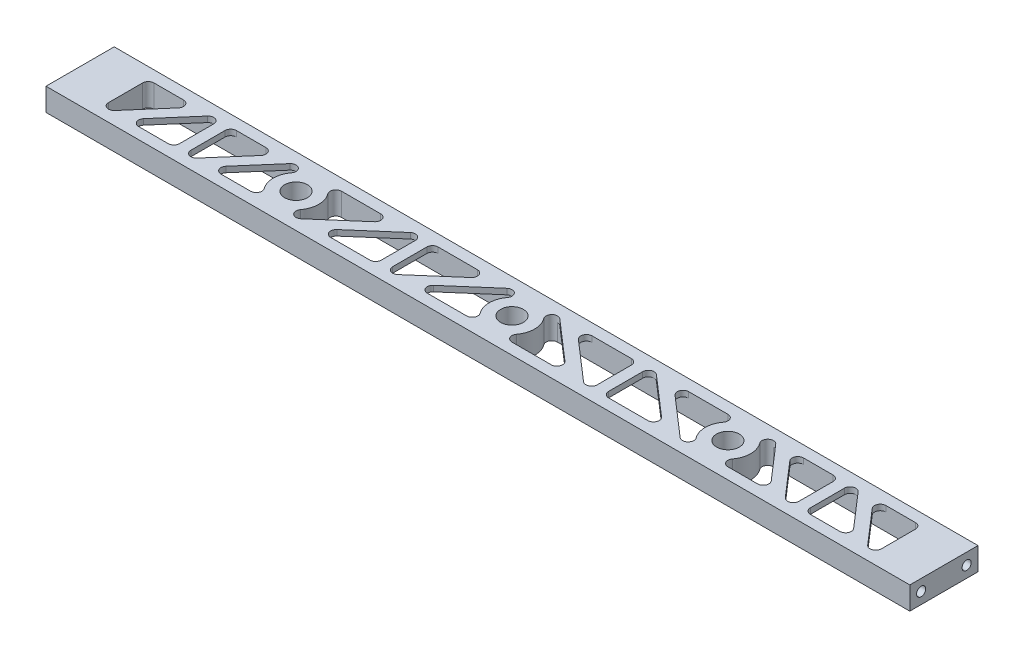
SolidWorks part; units mm, degrees
material "6061 Alloy"
ref_plane "Front Plane" through (0, 0, 0) normal (0, 0, 1) x (1, 0, 0)
ref_plane "Top Plane" through (0, 0, 0) normal (0, 1, 0) x (1, 0, 0)
ref_plane "Right Plane" through (0, 0, 0) normal (1, 0, 0) x (0, 0, -1)
sketch "Sketch1" plane through (0, 0, 0) normal (1, 0, 0) x (0, 0, -1)
  line L1 (-19.05, -6.35) -> (19.05, -6.35)
  line L2 (-19.05, -6.35) -> (-19.05, 6.35)
  line L3 (-19.05, 6.35) -> (19.05, 6.35)
  line L4 (19.05, -6.35) -> (19.05, 6.35)
  line L5 (-19.05, -6.35) -> (19.05, 6.35) construction
  line L6 (-19.05, 6.35) -> (19.05, -6.35) construction
  point P0 (0, 0)
  dimension "D1" = 38.1
  dimension "D2" = 12.7
extrude "Boss-Extrude1" add sketch "Sketch1" along normal mid plane 482.6
hole_wizard "1/4-20 Tapped Hole1" positions "3DSketch1" profile "Sketch3" tap size "1/4-20" standard "ANSI Inch"
sketch3d "3DSketch1"
  line L4 (241.3, 0, 19.05) -> (241.3, 0, 12.7) construction
  line L5 (241.3, 6.35, 19.05) -> (241.3, -6.35, 19.05) construction
  line L6 (241.3, 0, 12.7) -> (241.3, 0, -12.7) construction
  line L7 (241.3, 0, -12.7) -> (241.3, 0, -19.05) construction
  line L8 (241.3, -6.35, -19.05) -> (241.3, 6.35, -19.05) construction
  point P0 (241.3, 0, 12.7)
  point P2 (241.3, 0, -12.7)
  dimension "D1" = 25.4
sketch "Sketch3" plane through (241.3, 0, 12.7) normal (0, 1, 0) x (0, 0, -1)
  line L0 (0, 0) -> (0, 20.5838)
  line L1 (0, 20.5838) -> (2.5527, 19.05)
  line L2 (2.5527, 19.05) -> (2.5527, 0)
  line L5 (2.5527, 0) -> (0, 0)
  line L10 (0, 20.5838) -> (-2.5527, 19.05) construction
  line L11 (0, -6.35) -> (0, 107.95) construction
  dimension "Tap Drill Dia." = 5.1054
  dimension "Tap Drill Depth" = 19.05
  dimension "Drill Angle" = 118
sketch "Sketch2" plane through (0, 6.35, 0) normal (0, 1, 0) x (1, 0, 0)
  line L0 (0, 0) -> (241.3, 0) construction
  line L1 (241.3, -19.05) -> (241.3, 19.05) construction
  circle A0 centre (0, 0) radius 6.35
  circle A1 centre (120.65, 0) radius 6.35
  dimension "D1" = 12.7
extrude "Cut-Extrude1" cut sketch "Sketch2" against normal through all
sketch "Sketch4" plane through (0, -6.35, 0) normal (0, -1, 0) x (1, 0, 0)
  line L1 (12.7, 12.7) -> (107.95, 12.7)
  line L2 (133.35, 12.7) -> (212.725, 12.7)
  line L3 (215.9, 9.525) -> (215.9, -9.525)
  line L4 (212.725, -12.7) -> (133.35, -12.7)
  line L5 (107.95, -12.7) -> (12.7, -12.7)
  line L6 (241.3, 0) -> (215.9, 0) construction
  line L8 (241.3, 19.05) -> (241.3, -19.05) construction
  line L9 (241.3, 19.05) -> (-241.3, 19.05) construction
  arc A0 (10.16, -7.62) -> (10.16, 7.62) centre (0, 0) ccw
  arc A1 (110.49, 7.62) -> (110.49, -7.62) centre (120.65, 0) ccw
  arc A2 (130.81, 7.62) -> (130.81, -7.62) centre (120.65, 0) cw
  arc A3 (130.81, 7.62) -> (133.35, 12.7) centre (133.35, 9.525) cw
  arc A4 (130.81, -7.62) -> (133.35, -12.7) centre (133.35, -9.525) ccw
  arc A5 (110.49, -7.62) -> (107.95, -12.7) centre (107.95, -9.525) cw
  arc A6 (215.9, -9.525) -> (212.725, -12.7) centre (212.725, -9.525) cw
  arc A7 (212.725, 12.7) -> (215.9, 9.525) centre (212.725, 9.525) cw
  arc A8 (10.16, -7.62) -> (12.7, -12.7) centre (12.7, -9.525) ccw
  arc A9 (10.16, 7.62) -> (12.7, 12.7) centre (12.7, 9.525) cw
  arc A10 (110.49, 7.62) -> (107.95, 12.7) centre (107.95, 9.525) ccw
  dimension "D3" = 25.4
  dimension "D4" = 3.175
  dimension "D1" = 12.7
  dimension "D2" = 6.35
extrude "Cut-Extrude2" cut sketch "Sketch4" against normal blind 9.525
mirror "Mirror2" about plane through (0, 0, 0) normal (1, 0, 0) of "Cut-Extrude2", "Cut-Extrude1", "1/4-20 Tapped Hole1"
sketch "Sketch5" plane through (0, 3.175, 0) normal (0, -1, 0) x (1, 0, 0)
  line L0 (0, 19.05) -> (0, -19.05) construction
  line L1 (241.3, 19.05) -> (-241.3, 19.05) construction
  line L2 (241.3, -19.05) -> (-241.3, -19.05) construction
  line L3 (-107.95, -12.7) -> (-86.0338, -12.7)
  line L4 (-105.8671, 11.9213) -> (-83.9509, -7.1287)
  line L5 (-88.5912, 12.7) -> (-66.675, 12.7)
  line L6 (-63.5, 9.525) -> (-63.5, -9.525)
  line L7 (-90.6741, 7.1287) -> (-68.7579, -11.9213)
  line L8 (-83.9509, -7.1287) -> (-79.7851, -2.3362) construction
  line L9 (-107.95, 12.7) -> (-12.7, 12.7) construction
  line L10 (-12.7, -12.7) -> (-107.95, -12.7) construction
  line L11 (-12.7, 12.7) -> (-34.6162, 12.7)
  line L12 (-14.7829, -11.9213) -> (-36.6991, 7.1287)
  line L13 (-57.15, 9.525) -> (-57.15, -9.525)
  line L14 (-53.975, -12.7) -> (-32.0588, -12.7)
  line L15 (-51.8921, 11.9213) -> (-29.9759, -7.1287)
  line L16 (-29.9759, -7.1287) -> (-25.8101, -2.3362) construction
  line L17 (-63.5, 0) -> (-57.15, 0) construction
  line L18 (-133.35, 12.7) -> (-149.8751, 12.7)
  line L19 (-152.2734, 7.4445) -> (-135.7484, -11.6055)
  line L20 (-212.725, 12.7) -> (-133.35, 12.7) construction
  line L21 (-164.2891, 11.6055) -> (-147.7641, -7.4445)
  line L22 (-150.1624, -12.7) -> (-166.6875, -12.7)
  line L23 (-169.8625, 9.525) -> (-169.8625, -9.525)
  line L24 (-133.35, -12.7) -> (-212.725, -12.7) construction
  line L25 (-152.2734, 7.4445) -> (-157.0702, 3.2835) construction
  line L26 (-176.2125, 9.525) -> (-176.2125, -9.525)
  line L27 (-179.3875, 12.7) -> (-195.9126, 12.7)
  line L28 (-198.3109, 7.4445) -> (-181.7859, -11.6055)
  line L29 (-210.3266, 11.6055) -> (-193.8016, -7.4445)
  line L30 (-196.1999, -12.7) -> (-212.725, -12.7)
  line L31 (-215.9, -9.525) -> (-215.9, 9.525) construction
  line L32 (-215.9, -9.525) -> (-215.9, 9.525)
  line L33 (-169.8625, 0) -> (-176.2125, 0) construction
  line L34 (-198.3109, 7.4445) -> (-203.1077, 3.2835) construction
  arc A0 (-110.49, 7.62) -> (-110.49, -7.62) centre (-120.65, 0) cw
  arc A1 (-105.8671, 11.9213) -> (-110.49, 7.62) centre (-107.95, 9.525) ccw
  arc A2 (-107.95, -12.7) -> (-110.49, -7.62) centre (-107.95, -9.525) cw
  arc A3 (-86.0338, -12.7) -> (-83.9509, -7.1287) centre (-86.0338, -9.525) ccw
  arc A5 (-68.7579, -11.9213) -> (-63.5, -9.525) centre (-66.675, -9.525) ccw
  arc A6 (-66.675, 12.7) -> (-63.5, 9.525) centre (-66.675, 9.525) cw
  arc A7 (-88.5912, 12.7) -> (-90.6741, 7.1287) centre (-88.5912, 9.525) ccw
  arc A8 (-110.49, -7.62) -> (-110.49, 7.62) centre (-120.65, 0) ccw construction
  arc A9 (-10.16, 7.62) -> (-12.7, 12.7) centre (-12.7, 9.525) ccw construction
  arc A10 (-10.16, 7.62) -> (-10.16, -7.62) centre (0, 0) ccw construction
  arc A12 (-10.16, 7.62) -> (-12.7, 12.7) centre (-12.7, 9.525) ccw
  arc A13 (-10.16, 7.62) -> (-10.16, -7.62) centre (0, 0) ccw
  arc A14 (-14.7829, -11.9213) -> (-10.16, -7.62) centre (-12.7, -9.525) ccw
  arc A15 (-12.7, -12.7) -> (-10.16, -7.62) centre (-12.7, -9.525) ccw construction
  arc A16 (-34.6162, 12.7) -> (-36.6991, 7.1287) centre (-34.6162, 9.525) ccw
  arc A17 (-57.15, 9.525) -> (-51.8921, 11.9213) centre (-53.975, 9.525) cw
  arc A18 (-57.15, -9.525) -> (-53.975, -12.7) centre (-53.975, -9.525) ccw
  arc A19 (-32.0588, -12.7) -> (-29.9759, -7.1287) centre (-32.0588, -9.525) ccw
  arc A20 (-130.81, 7.62) -> (-130.81, -7.62) centre (-120.65, 0) ccw
  arc A21 (-130.81, 7.62) -> (-130.81, -7.62) centre (-120.65, 0) ccw construction
  arc A22 (-149.8751, 12.7) -> (-152.2734, 7.4445) centre (-149.8751, 9.525) ccw
  arc A23 (-130.81, -7.62) -> (-135.7484, -11.6055) centre (-133.35, -9.525) cw
  arc A24 (-133.35, -12.7) -> (-130.81, -7.62) centre (-133.35, -9.525) ccw construction
  arc A25 (-130.81, 7.62) -> (-133.35, 12.7) centre (-133.35, 9.525) ccw
  arc A26 (-130.81, 7.62) -> (-133.35, 12.7) centre (-133.35, 9.525) ccw construction
  arc A27 (-164.2891, 11.6055) -> (-169.8625, 9.525) centre (-166.6875, 9.525) ccw
  arc A28 (-150.1624, -12.7) -> (-147.7641, -7.4445) centre (-150.1624, -9.525) ccw
  arc A29 (-166.6875, -12.7) -> (-169.8625, -9.525) centre (-166.6875, -9.525) cw
  arc A30 (-215.9, -9.525) -> (-212.725, -12.7) centre (-212.725, -9.525) ccw construction
  arc A31 (-215.9, -9.525) -> (-212.725, -12.7) centre (-212.725, -9.525) ccw
  arc A32 (-215.9, 9.525) -> (-210.3266, 11.6055) centre (-212.725, 9.525) cw
  arc A33 (-212.725, 12.7) -> (-215.9, 9.525) centre (-212.725, 9.525) ccw construction
  arc A34 (-193.8016, -7.4445) -> (-196.1999, -12.7) centre (-196.1999, -9.525) cw
  arc A35 (-198.3109, 7.4445) -> (-195.9126, 12.7) centre (-195.9126, 9.525) cw
  arc A36 (-181.7859, -11.6055) -> (-176.2125, -9.525) centre (-179.3875, -9.525) ccw
  arc A37 (-176.2125, 9.525) -> (-179.3875, 12.7) centre (-179.3875, 9.525) ccw
  point P17 (-107.95, 12.7)
  point P27 (-66.675, -12.7)
  dimension "D1" = 3.175
  dimension "D2" = 6.35
extrude "Cut-Extrude3" cut sketch "Sketch5" against normal through all
mirror "Mirror3" about plane through (0, 0, 0) normal (1, 0, 0) of "Cut-Extrude3"
